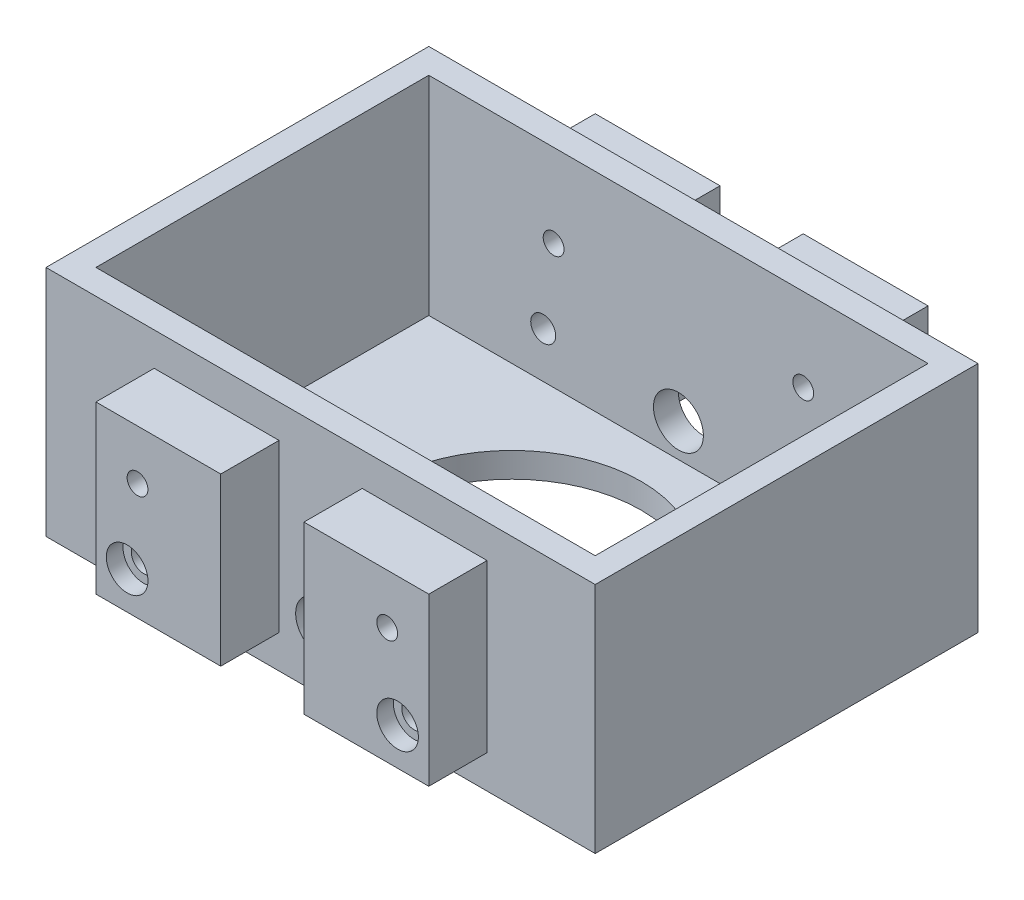
SolidWorks part; units mm, degrees
ref_plane "Front Plane" through (0, 0, 0) normal (0, 0, 1) x (1, 0, 0)
ref_plane "Top Plane" through (0, 0, 0) normal (0, 1, 0) x (1, 0, 0)
ref_plane "Right Plane" through (0, 0, 0) normal (1, 0, 0) x (0, 0, -1)
sketch "Sketch1" plane through (0, 0, 0) normal (0, 1, 0) x (1, 0, 0)
  line L1 (-41.3246, 5.1822) -> (24.6754, 5.1822)
  line L2 (-41.3246, 5.1822) -> (-41.3246, -40.8178)
  line L3 (-41.3246, -40.8178) -> (24.6754, -40.8178)
  line L4 (24.6754, 5.1822) -> (24.6754, -40.8178)
  dimension "D1" = 66
  dimension "D2" = 46
extrude "Boss-Extrude2" add sketch "Sketch1" along normal blind 3
sketch "Sketch3" plane through (0, 3, 0) normal (0, 1, 0) x (1, 0, 0)
  line L0 (-41.3246, 5.1822) -> (-41.3246, -40.8178) construction
  line L1 (-41.3246, 5.1822) -> (-38.3246, 5.1822)
  line L2 (-41.3246, 5.1822) -> (-41.3246, -40.8178)
  line L3 (-41.3246, -40.8178) -> (-38.3246, -40.8178)
  line L4 (-38.3246, 5.1822) -> (-38.3246, -40.8178)
  line L5 (-38.3246, 5.1822) -> (21.6754, 5.1822)
  line L6 (-38.3246, 5.1822) -> (-38.3246, 2.1822)
  line L7 (-38.3246, 2.1822) -> (21.6754, 2.1822)
  line L8 (21.6754, 5.1822) -> (21.6754, 2.1822)
  line L9 (21.6754, 5.1822) -> (24.6754, 5.1822)
  line L10 (21.6754, 5.1822) -> (21.6754, -40.8178)
  line L11 (21.6754, -40.8178) -> (24.6754, -40.8178)
  line L12 (24.6754, 5.1822) -> (24.6754, -40.8178)
  line L13 (-38.3246, -37.8178) -> (21.6754, -37.8178)
  line L14 (-38.3246, -37.8178) -> (-38.3246, -40.8178)
  line L15 (-38.3246, -40.8178) -> (21.6754, -40.8178)
  line L16 (21.6754, -37.8178) -> (21.6754, -40.8178)
  line L17 (24.6754, 5.1822) -> (-41.3246, 5.1822) construction
  line L18 (-41.3246, -40.8178) -> (24.6754, -40.8178) construction
  line L19 (24.6754, -40.8178) -> (24.6754, 5.1822) construction
  point P22 (23.1754, -40.8178)
  dimension "D1" = 3
  dimension "D2" = 3
  dimension "D3" = 3
  dimension "D4" = 3
  dimension "D5" = 0
  dimension "D6" = 0
  dimension "D7" = 0
  dimension "D8" = 0
  dimension "D9" = 0
  dimension "D10" = 0
  dimension "D11" = 0
  dimension "D12" = 0
  dimension "D13" = 0
  dimension "D14" = 0
  dimension "D15" = 0
  dimension "D16" = 0
extrude "Boss-Extrude4" add sketch "Sketch3" along normal blind 25 contours L8 L19 L4 L7 | L4 L19 L0 L17 | L13 L16 L15 L14 | L12 L11 L10 L9 region at (-39.8246, 3, 17.8178) region at (-8.3246, 3, -3.6822)
sketch "Sketch4" plane through (0, 0, 40.8178) normal (0, 0, 1) x (1, 0, 0)
  line L0 (24.6754, 28) -> (24.6754, 0) construction
  line L1 (-13.3246, 24) -> (-28.3246, 24)
  line L2 (-13.3246, 24) -> (-13.3246, 4)
  line L3 (-13.3246, 4) -> (-28.3246, 4)
  line L4 (-28.3246, 24) -> (-28.3246, 4)
  line L5 (-3.3246, 24) -> (11.6754, 24)
  line L6 (-3.3246, 24) -> (-3.3246, 4)
  line L7 (-3.3246, 4) -> (11.6754, 4)
  line L8 (11.6754, 24) -> (11.6754, 4)
  line L10 (-41.3246, 0) -> (24.6754, 0) construction
  line L11 (-41.3246, 28) -> (24.6754, 28) construction
  dimension "D1" = 15
  dimension "D2" = 20
  dimension "D3" = 15
  dimension "D4" = 20
  dimension "D5" = 10
  dimension "D6" = 13
  dimension "D7" = 4
  dimension "D8" = 4
extrude "Boss-Extrude5" add sketch "Sketch4" along normal blind 7 contours L8 L5 L6 L7 | L2 L1 L4 L3 region at (4.1754, 14, 40.8178)
sketch "Sketch5" plane through (0, 0, 47.8178) normal (0, 0, 1) x (1, 0, 0)
  line L0 (-41.3246, 28) -> (-41.3246, 0) construction
  line L1 (-41.3246, 28) -> (24.6754, 28) construction
  line L3 (24.6754, 28) -> (24.6754, 0) construction
  circle A2 centre (-24.5746, 8.5) radius 1.5
  circle A3 centre (7.9254, 8.5) radius 1.5
  circle A4 centre (6.6754, 18) radius 1.25
  circle A5 centre (-23.3246, 18) radius 1.25
  dimension "D5" = 16.75
  dimension "D9" = 3
  dimension "D10" = 2.5
  dimension "D11" = 3
  dimension "D12" = 2.5
  dimension "D1" = 32.5
  dimension "D2" = 30
  dimension "D3" = 9.5
  dimension "D4" = 9.5
  dimension "D6" = 10
  dimension "D7" = 16.75
  dimension "D8" = 18
extrude "Cut-Extrude1" cut sketch "Sketch5" against normal up to next
sketch "Sketch6" plane through (0, 0, -5.1822) normal (0, 0, -1) x (-1, 0, 0)
  line L0 (3.3246, 24) -> (-11.6754, 24)
  line L5 (3.3246, 24) -> (3.3246, 4)
  line L6 (3.3246, 4) -> (-11.6754, 4)
  line L7 (-11.6754, 24) -> (-11.6754, 4)
  line L8 (13.3246, 24) -> (28.3246, 24)
  line L9 (13.3246, 24) -> (13.3246, 4)
  line L10 (13.3246, 4) -> (28.3246, 4)
  line L11 (28.3246, 24) -> (28.3246, 4)
  line L13 (-24.6754, 28) -> (41.3246, 28) construction
  line L14 (41.3246, 28) -> (41.3246, 0) construction
  dimension "D1" = 20
  dimension "D2" = 15
  dimension "D3" = 15
  dimension "D4" = 20
  dimension "D5" = 10
  dimension "D6" = 4
  dimension "D7" = 13
  dimension "D8" = 4
extrude "Boss-Extrude6" add sketch "Sketch6" along normal blind 7 contours L0 L7 L6 L5 | L8 L11 L10 L9 region at (4.1754, 14, -5.1822)
sketch "Sketch7" plane through (0, 0, -12.1822) normal (0, 0, -1) x (-1, 0, 0)
  line L1 (-24.6754, 28) -> (-24.6754, 0) construction
  line L3 (-24.6754, 28) -> (41.3246, 28) construction
  circle A1 centre (-7.9254, 8.5) radius 1.5
  circle A2 centre (24.5746, 8.5) radius 1.5
  circle A3 centre (23.3246, 18) radius 1.25
  circle A4 centre (-6.6754, 18) radius 1.25
  dimension "D5" = 2.5
  dimension "D6" = 3
  dimension "D7" = 2.5
  dimension "D8" = 3
  dimension "D9" = 16.75
  dimension "D10" = 10
  dimension "D11" = 18
  dimension "D12" = 10
  dimension "D1" = 32.5
  dimension "D2" = 9.5
  dimension "D3" = 9.5
  dimension "D4" = 30
extrude "Cut-Extrude2" cut sketch "Sketch7" against normal blind 10
sketch "Sketch8" plane through (0, 0, 0) normal (0, -1, 0) x (-1, 0, 0)
  line L0 (-24.6754, 5.1822) -> (41.3246, 5.1822) construction
  line L1 (41.3246, 5.1822) -> (41.3246, -40.8178) construction
  circle A0 centre (8.3246, -17.8178) radius 15.5
  dimension "D1" = 31
  dimension "D2" = 23
  dimension "D3" = 33
extrude "Cut-Extrude3" cut sketch "Sketch8" against normal up to next contours A0
sketch "Sketch9" plane through (0, 0, -12.1822) normal (0, 0, -1) x (-1, 0, 0)
  circle A0 centre (-7.9254, 8.5) radius 2.5
  circle A1 centre (-7.9254, 8.5) radius 1.5 construction
  circle A2 centre (24.5746, 8.5) radius 2.5
  circle A3 centre (24.5746, 8.5) radius 1.5 construction
  dimension "D1" = 5
  dimension "D2" = 5
extrude "Cut-Extrude4" cut sketch "Sketch9" against normal blind 2
sketch "Sketch10" plane through (0, 0, 47.8178) normal (0, 0, 1) x (1, 0, 0)
  circle A0 centre (-24.5746, 8.5) radius 2.5
  circle A1 centre (-24.5746, 8.5) radius 1.5 construction
  circle A2 centre (7.9254, 8.5) radius 2.5
  circle A3 centre (7.9254, 8.5) radius 1.5 construction
  dimension "D1" = 5
  dimension "D2" = 5
extrude "Cut-Extrude5" cut sketch "Sketch10" against normal blind 2
sketch "Sketch11" plane through (0, 0, 40.8178) normal (0, 0, 1) x (1, 0, 0)
  line L0 (24.6754, 28) -> (24.6754, 0) construction
  line L1 (-41.3246, 0) -> (24.6754, 0) construction
  circle A0 centre (-8.3246, 7) radius 3
  dimension "D1" = 6
  dimension "D2" = 33
  dimension "D3" = 7
extrude "Cut-Extrude6" cut sketch "Sketch11" against normal through all and the other way through all
